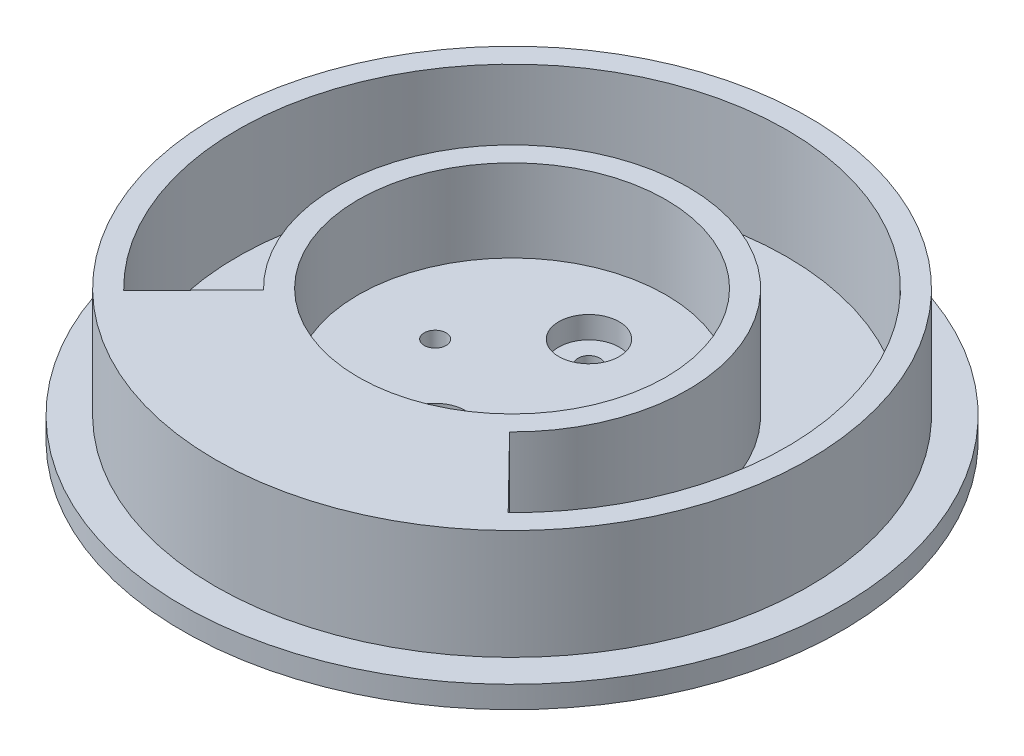
SolidWorks part; units mm, degrees
ref_plane "Front Plane" through (0, 0, 0) normal (0, 0, 1) x (1, 0, 0)
ref_plane "Top Plane" through (0, 0, 0) normal (0, 1, 0) x (1, 0, 0)
ref_plane "Right Plane" through (0, 0, 0) normal (1, 0, 0) x (0, 0, -1)
sketch "Sketch1" plane through (0, 0, 0) normal (0, 1, 0) x (1, 0, 0)
  line L0 (-17.5, -17.8536) -> (-11.2, -11.4263)
  line L1 (0, -55) -> (0, 55) construction
  line L2 (17.5, -17.8536) -> (11.2, -11.4263)
  line L4 (-17.5, -17.8536) -> (3.8221, -38.7535) construction
  circle A0 centre (0, 0) radius 27
  arc A1 (11.2, -11.4263) -> (-11.2, -11.4263) centre (0, 0) ccw
  arc A2 (17.5, -17.8536) -> (-17.5, -17.8536) centre (0, 0) ccw
  circle A3 centre (0, 0) radius 14
  arc A4 (16.5039, 11.7639) -> (14.35, -14.6399) centre (0.1913, -0.1952) cw construction
  circle A5 centre (0, 0) radius 19.9533 construction
  dimension "D1" = 54
  dimension "D2" = 2
  dimension "D3" = 9
  dimension "D4" = 2
  dimension "D5" = 35
extrude "Boss-Extrude1" add sketch "Sketch1" along normal blind 10
sketch "Sketch2" plane through (0, 0, 0) normal (0, -1, 0) x (1, 0, 0)
  circle A0 centre (0, 0) radius 30
  circle A1 centre (0, 0) radius 14 construction
  circle A2 centre (0, 0) radius 14 construction
  dimension "D1" = 60
extrude "Boss-Extrude2" add sketch "Sketch2" along normal blind 2
sketch "Sketch3" plane through (0, 0, 0) normal (0, 1, 0) x (1, 0, 0)
  line L0 (0, -13.5729) -> (0, 13.5729) construction
  line L1 (-2.5, 29.8) -> (2.5, 29.8)
  line L2 (-2.5, 29.8) -> (-2.5, 25.4032)
  line L3 (-2.5, 25.4032) -> (2.5, 25.4032)
  line L4 (2.5, 29.8) -> (2.5, 25.4032)
  line L5 (-2.5, 29.8) -> (2.5, 25.4032) construction
  line L6 (-2.5, 25.4032) -> (2.5, 29.8) construction
  line L7 (29.8, 2.5) -> (25.4032, 2.5)
  line L8 (29.8, 2.5) -> (29.8, -2.5)
  line L9 (29.8, -2.5) -> (25.4032, -2.5)
  line L10 (25.4032, 2.5) -> (25.4032, -2.5)
  line L11 (2.5, -29.8) -> (2.5, -25.4032)
  line L12 (2.5, -29.8) -> (-2.5, -29.8)
  line L13 (-2.5, -29.8) -> (-2.5, -25.4032)
  line L14 (2.5, -25.4032) -> (-2.5, -25.4032)
  line L15 (-29.8, -2.5) -> (-25.4032, -2.5)
  line L16 (-29.8, -2.5) -> (-29.8, 2.5)
  line L17 (-29.8, 2.5) -> (-25.4032, 2.5)
  line L18 (-25.4032, -2.5) -> (-25.4032, 2.5)
  circle A1 centre (0, 0) radius 27 construction
  point P0 (0, 27.6016)
  dimension "D2" = 29.8
  dimension "D1" = 5
  dimension "D3" = 4
extrude "Boss-Extrude3" [suppressed] add sketch "Sketch3" along normal blind 10
sketch "Sketch5" [suppressed] plane through (0, 0, 0) normal (0, 1, 0) x (1, 0, 0)
  line L0 (0, 29.8) -> (0, 32.5)
  line L1 (2.5, 29.8) -> (-2.5, 29.8) construction
  line L2 (0, -6.6) -> (0, 6.6) construction
  line L3 (0, -29.8) -> (0, -32.5)
  line L4 (0, 29.8) -> (-2.5, 29.8)
  line L5 (-2.5, 29.8) -> (-2.5, 26.884)
  line L6 (-26.884, 2.5) -> (-29.8, 2.5)
  line L7 (-29.8, 2.5) -> (-29.8, -2.5)
  line L8 (-29.8, -2.5) -> (-26.884, -2.5)
  line L9 (-2.5, -26.884) -> (-2.5, -29.8)
  line L10 (-2.5, -29.8) -> (0, -29.8)
  line L11 (-2.5, -29.8) -> (2.5, -29.8) construction
  circle A0 centre (0, 0) radius 32.5 construction
  arc A1 (0, 32.5) -> (0, -32.5) centre (0, 0) ccw
  arc A2 (-26.884, 2.5) -> (-2.5, 26.884) centre (0, 0) cw
  arc A3 (-26.884, -2.5) -> (-2.5, -26.884) centre (0, 0) ccw
extrude "Boss-Extrude4" [suppressed] add sketch "Sketch5" along normal up to surface (10 mm away) up to face at (0, 10, 27)
ref_plane "Plane1" through (0, 2.5, 0) normal (0, 1, 0) x (1, 0, 0)
sketch "Sketch6" plane through (0, 2.5, 0) normal (0, 1, 0) x (1, 0, 0)
  circle A0 centre (0, 0) radius 14
extrude "Boss-Extrude5" add sketch "Sketch6" against normal up to surface (2.5 mm away) up to face at (0, 0, 14)
sketch "Sketch4" plane through (0, -2, 0) normal (0, -1, 0) x (1, 0, 0)
  circle A0 centre (0, 0) radius 7 construction
  circle A1 centre (0, -7) radius 1
  circle A2 centre (-7, 0) radius 1
  circle A3 centre (0, 7) radius 1
  circle A4 centre (7, 0) radius 1
  point P14 (0, 0)
  dimension "D1" = 14
  dimension "D2" = 2
  dimension "D3" = 4
extrude "Cut-Extrude1" cut sketch "Sketch4" against normal through all both and the other way through all
sketch "Sketch7" plane through (0, 10, 0) normal (0, 1, 0) x (1, 0, 0)
  line L0 (11.2, -11.4263) -> (17.5, -17.8536) construction
  circle A0 centre (0, 0) radius 20.5 construction
  circle A1 centre (0, -20.5) radius 1.6
  point P5 (14.35, -14.6399)
  dimension "D1" = 3.2
extrude "Cut-Extrude2" [suppressed] cut sketch "Sketch7" against normal through all both and the other way through all
sketch "Sketch8" [suppressed] plane through (0, -2, 0) normal (0, -1, 0) x (1, 0, 0)
  line L0 (6.6, 0) -> (-6.6, 0) construction
  line L1 (-3.1177, 20.5) -> (-1.5588, 17.8)
  line L2 (-1.5588, 17.8) -> (1.5588, 17.8)
  line L3 (1.5588, 17.8) -> (3.1177, 20.5)
  line L4 (3.1177, 20.5) -> (1.5588, 23.2)
  line L5 (1.5588, 23.2) -> (-1.5588, 23.2)
  line L6 (-1.5588, 23.2) -> (-3.1177, 20.5)
  circle A0 centre (0, 20.5) radius 2.7 construction
  dimension "D1" = 5.4
extrude "Cut-Extrude3" [suppressed] cut sketch "Sketch8" against normal blind 4
sketch "Sketch9" [suppressed] plane through (0, 0, 0) normal (1, 0, 0) x (0, 0, -1)
  line L0 (32.5, 10) -> (-32.5, 10) construction
  line L1 (36, -2) -> (30.5, -2)
  line L3 (36, 10) -> (30.5, 10)
  line L4 (30.5, -2) -> (30.5, 10)
  line L5 (32.5, 10) -> (32.5, 0) construction
  arc A0 (36, -2) -> (36, 10) centre (36, 4) ccw
  circle A1 centre (36, 4) radius 1.6
  circle A2 centre (36, 4) radius 3 construction
  dimension "D4" = 3.2
  dimension "D5" = 6
  dimension "D1" = 3.5
  dimension "D2" = 2
  dimension "D3" = 12
extrude "Boss-Extrude6" [suppressed] add sketch "Sketch9" against normal blind 2
mirror "Mirror1" [suppressed] about plane through (0, 0, 0) normal (0, 0, 1)
sketch "Sketch10" plane through (0, 2.5, 0) normal (0, 1, 0) x (1, 0, 0)
  circle A0 centre (0, 7) radius 2.75
  circle A1 centre (0, -7) radius 2.75
  dimension "D1" = 5.5
  dimension "D2" = 5.5
extrude "Cut-Extrude4" cut sketch "Sketch10" against normal blind 2
sketch "Sketch11" plane through (0, -2, 0) normal (0, -1, 0) x (1, 0, 0)
  circle A0 centre (0, 0) radius 4.25
  dimension "D1" = 8.5
extrude "Cut-Extrude5" cut sketch "Sketch11" against normal blind 1
